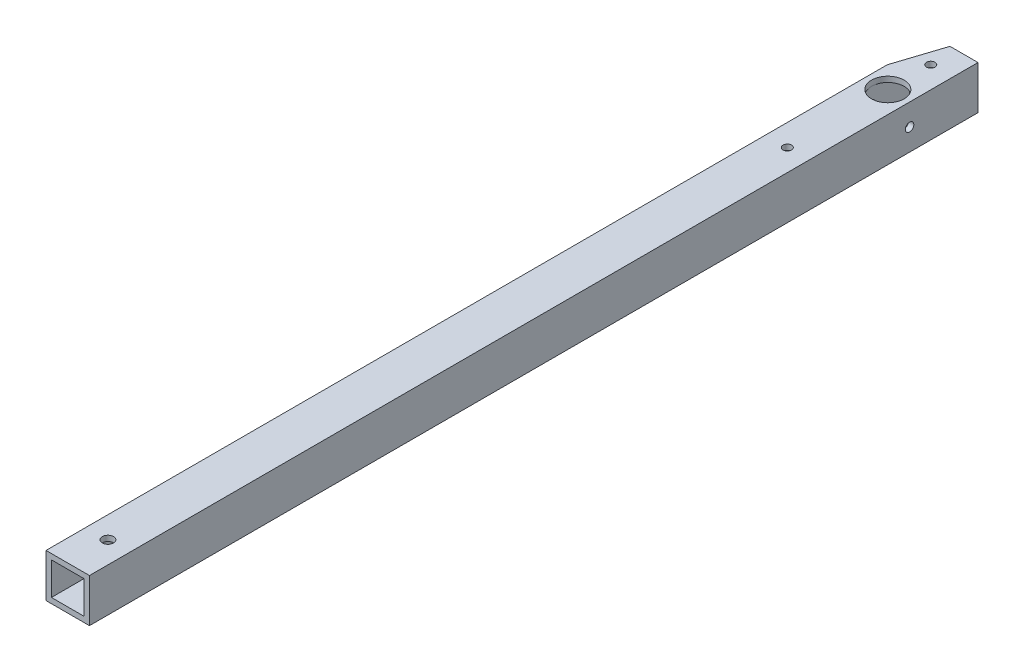
SolidWorks part; units mm, degrees
ref_plane "Front Plane" through (0, 0, 0) normal (0, 0, 1) x (1, 0, 0)
ref_plane "Top Plane" through (0, 0, 0) normal (0, 1, 0) x (1, 0, 0)
ref_plane "Right Plane" through (0, 0, 0) normal (1, 0, 0) x (0, 0, -1)
sketch "Sketch1" plane through (0, 0, 0) normal (0, 0, 1) x (1, 0, 0)
  line L0 (-9.525, 9.525) -> (9.525, 9.525)
  line L2 (-12.7, 12.7) -> (12.7, 12.7)
  line L3 (-12.7, 12.7) -> (-12.7, -12.7)
  line L4 (-12.7, -12.7) -> (12.7, -12.7)
  line L5 (12.7, 12.7) -> (12.7, -12.7)
  line L10 (9.525, 9.525) -> (9.525, -9.525)
  line L11 (-9.525, -9.525) -> (9.525, -9.525)
  line L12 (-9.525, 9.525) -> (-9.525, -9.525)
  point P12 (0, 12.7)
  point P14 (12.7, 0)
  dimension "Wall Thickness" = 3.175
  dimension "Outside Width" = 25.4
  dimension "Outside Height" = 25.4
  dimension "Inside Height" = 19.05
  dimension "Inside Width" = 19.05
sketch "Sketch2" plane through (0, 0, 0) normal (1, 0, 0) x (0, 0, -1)
  line L0 (266.7, 0) -> (-266.7, 0)
  point P4 (0, 0)
  point P7 (-266.7, 0)
  point P10 (266.7, 0)
  dimension "Length" = 533.4
sketch "Sketch3" plane through (0, 0, 0) normal (0, 0, 1) x (1, 0, 0)
  line L21 (12.7, 12.7) -> (-12.7, 12.7)
  line L22 (12.7, -12.7) -> (12.7, 12.7)
  line L23 (-12.7, -12.7) -> (12.7, -12.7)
  line L24 (-12.7, 12.7) -> (-12.7, -12.7)
  line L25 (12.7, 12.7) -> (-12.7, 12.7)
  line L26 (12.7, -12.7) -> (12.7, 12.7)
  line L27 (-12.7, -12.7) -> (12.7, -12.7)
  line L28 (-12.7, 12.7) -> (-12.7, -12.7)
  line L29 (9.525, 9.525) -> (-9.525, 9.525)
  line L30 (9.525, -9.525) -> (9.525, 9.525)
  line L31 (-9.525, -9.525) -> (9.525, -9.525)
  line L32 (-9.525, 9.525) -> (-9.525, -9.525)
  line L33 (9.525, 9.525) -> (-9.525, 9.525)
  line L34 (9.525, -9.525) -> (9.525, 9.525)
  line L35 (-9.525, -9.525) -> (9.525, -9.525)
  line L36 (-9.525, 9.525) -> (-9.525, -9.525)
  dimension "D1" = 0
  dimension "D2" = 0
extrude "Boss-Extrude1" add sketch "Sketch3" along normal up to vertex (266.7 mm away) and the other way up to vertex (266.7 mm away) up to point (0, 0, 266.7) other way up to point (0, 0, -266.7)
sketch "Drawing Reference" plane through (0, 0, 0) normal (1, 0, 0) x (0, 0, -1)
  line L0 (-266.7, 0) -> (266.7, 0) construction
  line L1 (0, -12.7) -> (0, 12.7) construction
  line L2 (-266.7, -12.7) -> (266.7, -12.7) construction
  line L5 (-266.7, 12.7) -> (266.7, 12.7) construction
  point P7 (-248.412, 0)
  point P8 (248.412, 0)
  dimension "D1" = 18.288
sketch "Sketch4" plane through (0, 12.7, 0) normal (0, 1, 0) x (1, 0, 0)
  line L1 (0, 266.7) -> (0, 212.725) construction
  line L7 (-12.7, 225.0135) -> (-12.7, 266.7)
  line L8 (-188.9197, -317.3351) -> (4.6184, 278.3139) construction
  line L10 (-12.7, -266.7) -> (-12.7, 266.7) construction
  line L11 (-12.7, 266.7) -> (12.7, 266.7)
  line L12 (12.7, 266.7) -> (12.7, 252.73)
  line L13 (12.7, -266.7) -> (12.7, 266.7) construction
  line L14 (12.7, 252.73) -> (-3.6943, 252.73)
  line L15 (-3.6943, 252.73) -> (-12.7, 225.0135)
  circle A0 centre (0, 212.725) radius 9.525
  dimension "D1" = 13.97
extrude "Cut-Extrude1" cut sketch "Sketch4" against normal blind 25.4
sketch "Sketch5" plane through (0, -12.7, 0) normal (0, -1, 0) x (1, 0, 0)
  circle A0 centre (0.3539, -181.928) radius 9.525
extrude "Cut-Extrude2" cut sketch "Sketch5" against normal blind 3.175
sketch "Sketch6" plane through (12.7, 0, 0) normal (1, 0, 0) x (0, 0, -1)
  line L0 (252.73, 0) -> (212.725, 0) construction
  line L1 (252.73, -12.7) -> (252.73, 12.7) construction
hole_wizard "#10 Clearance Hole1" positions "Sketch7" profile "Sketch8" hole size "#10" standard "ANSI Inch" end condition through all
sketch "Sketch7" plane through (12.7, 0, 0) normal (1, 0, 0) x (0, 0, -1)
  point P0 (212.725, 0)
sketch "Sketch8" plane through (12.7, 0, -212.725) normal (0, 1, 0) x (0, 0, -1)
  line L0 (0, 0) -> (0, 25.4)
  line L1 (0, 25.4) -> (2.4892, 25.4)
  line L2 (2.4892, 25.4) -> (2.4892, 0)
  line L5 (2.4892, 0) -> (0, 0)
  line L11 (0, -6.35) -> (0, 107.95) construction
  dimension "Thru Hole Dia." = 4.9784
  dimension "Thru Hole Depth" = 25.4
hole_wizard "#10 Clearance Hole2" positions "Sketch9" profile "Sketch10" hole size "#10" standard "ANSI Inch" end condition through all
sketch "Sketch9" plane through (0, 12.7, 0) normal (0, 1, 0) x (1, 0, 0)
  point P0 (0, 153.96)
  point P3 (0, 237.8065)
sketch "Sketch10" plane through (0, 12.7, -153.96) normal (1, 0, 0) x (0, 0, 1)
  line L0 (0, 0) -> (0, 25.4)
  line L1 (0, 25.4) -> (2.4892, 25.4)
  line L2 (2.4892, 25.4) -> (2.4892, 0)
  line L5 (2.4892, 0) -> (0, 0)
  line L11 (0, -6.35) -> (0, 107.95) construction
  dimension "Thru Hole Dia." = 4.9784
  dimension "Thru Hole Depth" = 25.4
hole_wizard "1/4 Clearance Hole2" positions "Sketch13" profile "Sketch14" hole size "1/4" standard "ANSI Inch" end condition through all
sketch "Sketch13" plane through (0, 12.7, 0) normal (0, 1, 0) x (1, 0, 0)
  point P0 (0, -243.2081)
sketch "Sketch14" plane through (0, 12.7, 243.2081) normal (1, 0, 0) x (0, 0, 1)
  line L0 (0, 0) -> (0, 25.4)
  line L1 (0, 25.4) -> (3.2639, 25.4)
  line L2 (3.2639, 25.4) -> (3.2639, 0)
  line L5 (3.2639, 0) -> (0, 0)
  line L11 (0, -6.35) -> (0, 107.95) construction
  dimension "Thru Hole Dia." = 6.5278
  dimension "Thru Hole Depth" = 25.4
equation "\"D1@Drawing Reference\"=\"Outside Width@Sketch1\" * 0.72"
